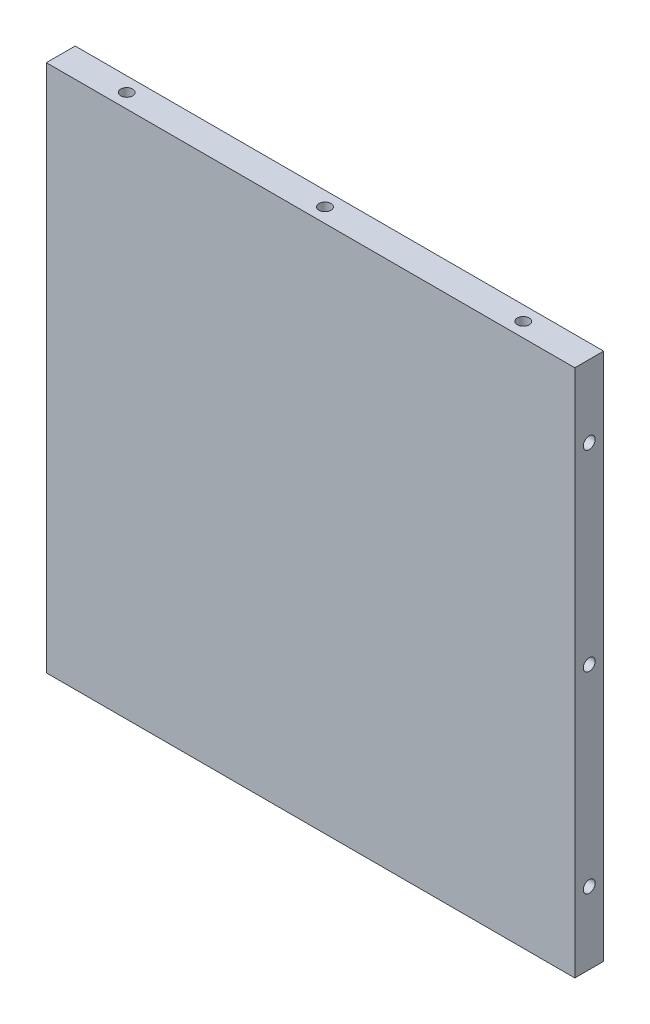
SolidWorks part; units mm, degrees
ref_plane "Спереди" through (0, 0, 0) normal (0, 0, 1) x (1, 0, 0)
ref_plane "Сверху" through (0, 0, 0) normal (0, 1, 0) x (1, 0, 0)
ref_plane "Справа" through (0, 0, 0) normal (1, 0, 0) x (0, 0, -1)
sketch "Эскиз1" plane through (0, 0, 0) normal (0, 0, 1) x (1, 0, 0)
  line L1 (0, 0) -> (146.6, 0)
  line L2 (0, 0) -> (0, 146.6)
  line L3 (0, 146.6) -> (146.6, 146.6)
  line L4 (146.6, 0) -> (146.6, 146.6)
  dimension "D1" = 146.6
  dimension "D2" = 146.6
extrude "Бобышка-Вытянуть1" add sketch "Эскиз1" along normal blind 8
sketch "Эскиз2" plane through (0, 0, 0) normal (0, -1, 0) x (1, 0, 0)
  line L0 (0, 0) -> (146.6, 0) construction
  line L1 (0, 8) -> (0, 0) construction
  circle A0 centre (18.3, 4) radius 1.65
  circle A1 centre (73.3, 4) radius 1.65
  circle A2 centre (128.3, 4) radius 1.65
  dimension "D1" = 3.3
  dimension "D2" = 4
  dimension "D3" = 18.3
  dimension "D4" = 3
extrude "Вырез-Вытянуть1" cut sketch "Эскиз2" against normal through all
sketch "Эскиз3" plane through (0, 0, 0) normal (-1, 0, 0) x (0, 0, 1)
  line L0 (0, 146.6) -> (0, 0) construction
  line L1 (8, 0) -> (0, 0) construction
  circle A0 centre (4, 20) radius 1.65
  circle A1 centre (4, 73.3) radius 1.65
  circle A2 centre (4, 126.6) radius 1.65
  dimension "D1" = 3.3
  dimension "D2" = 4
  dimension "D3" = 20
  dimension "D4" = 3
extrude "Вырез-Вытянуть2" cut sketch "Эскиз3" against normal through all
sketch "Эскиз4" plane through (0, 0, 8) normal (0, 0, 1) x (1, 0, 0)
  line L0 (146.6, 0) -> (146.6, 146.6) construction
  line L1 (15, 131.6) -> (131.6, 131.6)
  line L2 (15, 131.6) -> (15, 15)
  line L3 (15, 15) -> (131.6, 15)
  line L4 (131.6, 131.6) -> (131.6, 15)
  line L5 (0, 146.6) -> (0, 0) construction
  line L6 (146.6, 146.6) -> (0, 146.6) construction
  line L7 (0, 0) -> (146.6, 0) construction
  dimension "D1" = 15
  dimension "D2" = 15
  dimension "D3" = 15
  dimension "D4" = 15
extrude "Бобышка-Вытянуть2" add sketch "Эскиз4" against normal up to surface (8 mm away) up to face at (73.3, 73.3, 0)
